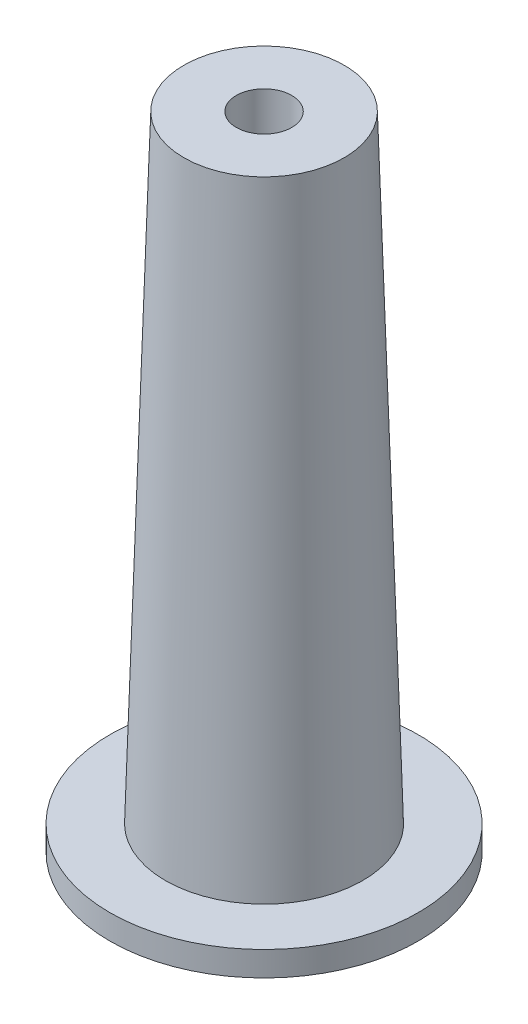
SolidWorks part; units mm, degrees
ref_plane "Front Plane" through (0, 0, 0) normal (0, 0, 1) x (1, 0, 0)
ref_plane "Top Plane" through (0, 0, 0) normal (0, 1, 0) x (1, 0, 0)
ref_plane "Right Plane" through (0, 0, 0) normal (1, 0, 0) x (0, 0, -1)
sketch "Esquisse1" plane through (0, 0, 0) normal (0, 1, 0) x (1, 0, 0)
  circle A0 centre (0, 0) radius 25
extrude "Boss.-Extru.1" add sketch "Esquisse1" along normal blind 4
sketch "Esquisse2" plane through (0, 4, 0) normal (0, 1, 0) x (1, 0, 0)
  circle A0 centre (0, 0) radius 4.5
ref_plane "Plan1" through (0, 0, 0) normal (1, 0, 0) x (0, 0, -1)
ref_axis "Axe1" through (0, 4, 0) along (0, 1, 0)
sketch "Esquisse3" plane through (0, 0, 0) normal (1, 0, 0) x (0, 0, -1)
  line L0 (0, 4) -> (-16, 4)
  line L1 (-16, 4) -> (-13, 104)
  line L2 (-13, 104) -> (0, 104)
  line L3 (0, 104) -> (0, 4)
  dimension "D1" = 100
  dimension "D2" = 13
  dimension "D3" = 16
revolve "Révolution1" add sketch "Esquisse3" angle 360 about L3
extrude "Enlèv. mat.-Extru.1" cut sketch "Esquisse2" against normal through all and the other way through all
